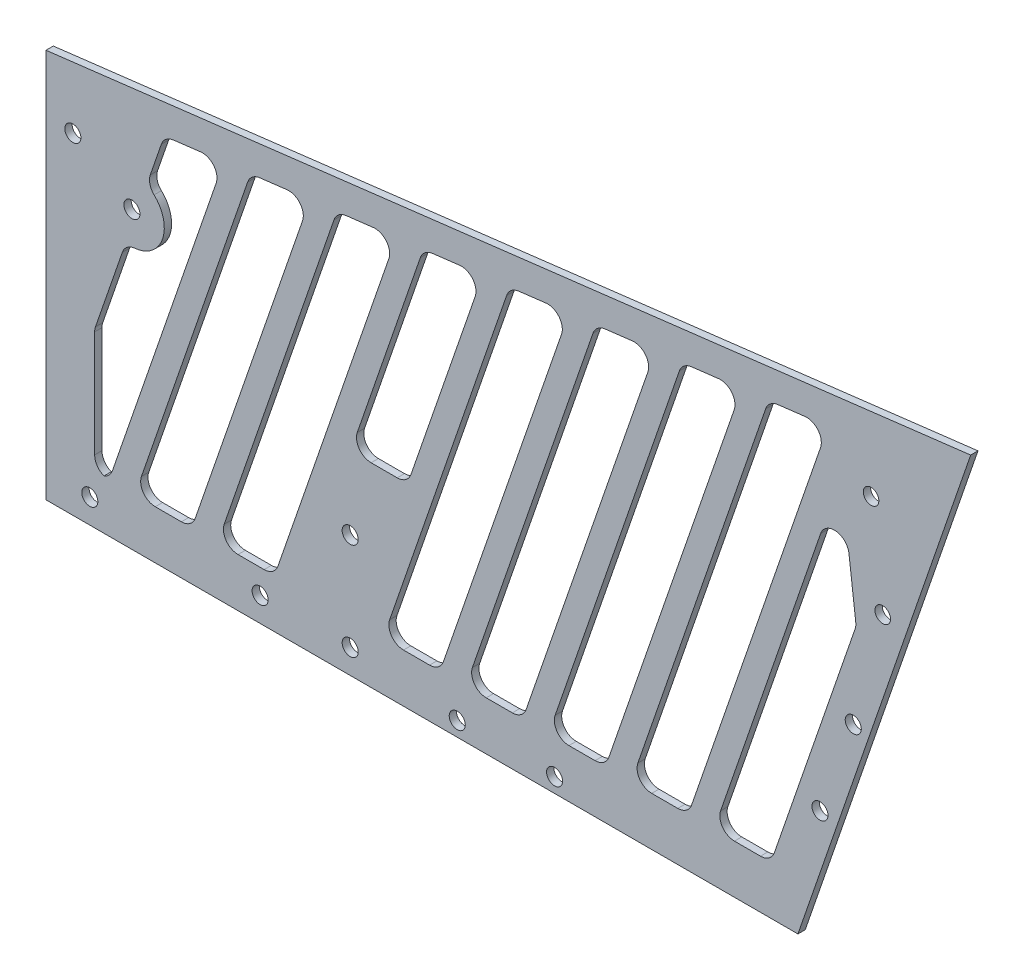
SolidWorks part; units mm, degrees
other "标注1"
sketch "草图8" plane through (190, 0, 1.5) normal (0.4662, -0.1687, 0.8685) x (0.883, 0.0286, -0.4684)
material "自定义塑料"
ref_plane "前视基准面" through (0, 0, 0) normal (0, 0, 1) x (1, 0, 0)
ref_plane "上视基准面" through (0, 0, 0) normal (0, 1, 0) x (1, 0, 0)
ref_plane "右视基准面" through (0, 0, 0) normal (1, 0, 0) x (0, 0, -1)
sketch "草图1" plane through (0, 0, 0) normal (0, 0, 1) x (1, 0, 0)
  line L0 (44, 5) -> (9, 5) construction
  line L1 (0, 0) -> (49, 0)
  line L2 (0, 0) -> (0, 80)
  line L5 (49, 0) -> (154.5, 0)
  line L6 (154.5, 0) -> (190, 102.9694)
  line L7 (0, 80) -> (190, 102.9694)
  circle A0 centre (44, 5) radius 1.65
  circle A1 centre (9, 5) radius 1.65
  circle A2 centre (62.5, 5) radius 1.65
  circle A3 centre (62.5, 25) radius 1.65
  circle A4 centre (84.5, 3) radius 1.65
  circle A5 centre (104.5, 3) radius 1.65
  circle A6 centre (159.0292, 24.1724) radius 1.65
  circle A7 centre (165.8696, 42.9663) radius 1.65
  circle A8 centre (5.5167, 68) radius 1.65
  point P9 (173.819, 56.0356)
  dimension "D3" = 3.3
  dimension "D4" = 190
  dimension "D1" = 49
  dimension "D2" = 80
  dimension "D5" = 5
  dimension "D6" = 35
  dimension "D7" = 105.5
extrude "凸台-拉伸1" add sketch "草图1" along normal blind 1.5
sketch "草图2" plane through (0, 0, 0) normal (0, 0, -1) x (-1, 0, 0)
  circle A0 centre (-17.6548, 60.5226) radius 1.65
  dimension "D1" = 3.3
  dimension "D2" = 60.5226
  dimension "D3" = 17.6548
extrude "切除-拉伸1" cut sketch "草图2" against normal through all
sketch "草图5" plane through (0, 0, 1.5) normal (0, 0, 1) x (1, 0, 0)
  line L0 (0, 80) -> (0, 0) construction
  line L1 (0, 0) -> (154.5, 0) construction
  circle A0 centre (169.5262, 85.385) radius 1.6
  circle A1 centre (171.9266, 65.5296) radius 1.6
  dimension "D1" = 3.2
  dimension "D2" = 169.5262
  dimension "D3" = 171.9266
  dimension "D4" = 65.5296
  dimension "D5" = 85.385
extrude "切除-拉伸3" cut sketch "草图5" against normal through all
sketch "草图6" plane through (0, 0, 0) normal (0, 0, -1) x (-1, 0, 0)
  line L0 (-154.5, 10) -> (0, 10)
  line L1 (-10, 0) -> (-10, 80)
  line L2 (-0.7201, 74.0434) -> (-181.2031, 95.8622)
  line L3 (-181.2031, 95.8622) -> (-148.8277, 1.9556)
  line L4 (0, 0) -> (0, 80)
  line L5 (-154.5, 0) -> (0, 0)
  line L6 (-190, 102.9694) -> (-154.5, 0)
  line L7 (0, 80) -> (-190, 102.9694)
  line L8 (0, 0) -> (0, 80)
  line L9 (-154.5, 0) -> (0, 0)
  line L10 (-190, 102.9694) -> (-154.5, 0)
  line L11 (0, 80) -> (-190, 102.9694)
  line L12 (-162.4894, 93.5999) -> (-167.1453, 55.0868)
  line L13 (-164.2031, 95.8622) -> (-131.8277, 1.9556)
  line L14 (-147.2031, 95.8622) -> (-114.8277, 1.9556)
  line L15 (-130.2031, 95.8622) -> (-97.8277, 1.9556)
  line L16 (-113.2031, 95.8622) -> (-80.8277, 1.9556)
  line L17 (-96.2031, 95.8622) -> (-63.8277, 1.9556)
  line L18 (-79.2031, 95.8622) -> (-46.8277, 1.9556)
  line L19 (-62.2031, 95.8622) -> (-29.8277, 1.9556)
  line L20 (-45.2031, 95.8622) -> (-12.8277, 1.9556)
  line L21 (-28.2031, 95.8622) -> (4.1723, 1.9556)
  line L22 (-166.5666, 95.0474) -> (-134.1912, 1.1408)
  line L23 (-149.5666, 95.0474) -> (-117.1912, 1.1408)
  line L24 (-132.5666, 95.0474) -> (-100.1912, 1.1408)
  line L25 (-115.5666, 95.0474) -> (-83.1912, 1.1408)
  line L26 (-98.5666, 95.0474) -> (-66.1912, 1.1408)
  line L27 (-81.5666, 95.0474) -> (-49.1912, 1.1408)
  line L28 (-64.5666, 95.0474) -> (-32.1912, 1.1408)
  line L29 (-47.5666, 95.0474) -> (-15.1912, 1.1408)
  line L30 (-30.5666, 95.0474) -> (1.8088, 1.1408)
  line L31 (-161.8397, 96.6771) -> (-129.4642, 2.7705)
  line L32 (-144.8397, 96.6771) -> (-112.4642, 2.7705)
  line L33 (-127.8397, 96.6771) -> (-95.4642, 2.7705)
  line L34 (-110.8397, 96.6771) -> (-78.4642, 2.7705)
  line L35 (-93.8397, 96.6771) -> (-61.4642, 2.7705)
  line L36 (-76.8397, 96.6771) -> (-44.4642, 2.7705)
  line L37 (-59.8397, 96.6771) -> (-27.4642, 2.7705)
  line L38 (-42.8397, 96.6771) -> (-10.4642, 2.7705)
  line L39 (-25.8397, 96.6771) -> (6.5358, 2.7705)
  line L40 (-178.8397, 96.6771) -> (-146.4642, 2.7705)
  circle A0 centre (-169.5262, 85.385) radius 1.6 construction
  circle A1 centre (-171.9266, 65.5296) radius 1.6 construction
  circle A2 centre (-165.8696, 42.9663) radius 1.5 construction
  circle A3 centre (-159.0292, 24.1724) radius 1.5 construction
  circle A4 centre (-104.5, 3) radius 1.65 construction
  circle A5 centre (-84.5, 3) radius 1.65 construction
  circle A6 centre (-62.5, 5) radius 1.65 construction
  circle A7 centre (-44, 5) radius 1.65 construction
  circle A8 centre (-62.5, 25) radius 1.65 construction
  circle A9 centre (-9, 5) radius 1.65 construction
  circle A10 centre (-17.6548, 60.5226) radius 1.65 construction
  circle A11 centre (-5.5167, 68) radius 1.65 construction
  circle A12 centre (-169.5262, 85.385) radius 1.6
  circle A13 centre (-171.9266, 65.5296) radius 1.6
  circle A14 centre (-165.8696, 42.9663) radius 1.5
  circle A15 centre (-159.0292, 24.1724) radius 1.5
  circle A16 centre (-104.5, 3) radius 1.65
  circle A17 centre (-84.5, 3) radius 1.65
  circle A18 centre (-62.5, 5) radius 1.65
  circle A19 centre (-44, 5) radius 1.65
  circle A20 centre (-62.5, 25) radius 1.65
  circle A21 centre (-9, 5) radius 1.65
  circle A22 centre (-17.6548, 60.5226) radius 1.65
  circle A23 centre (-5.5167, 68) radius 1.65
  circle A24 centre (-17.6548, 60.5226) radius 6.65
  circle A25 centre (-62.5, 25) radius 6.65
  dimension "D5" = 6
  dimension "D1" = 0
  dimension "D2" = 10
  dimension "D3" = 10
  dimension "D4" = 6
  dimension "D7" = 2.5
  dimension "D8" = 2.5
  dimension "D9" = 5
  dimension "D10" = 2.5
  dimension "D6" = 10
extrude "切除-拉伸4" cut sketch "草图6" against normal blind 10 contours A24 L30 L2 L38 L0 L1 | L2 L37 L0 L29 | L2 L36 L0 L28 | A25 L27 L2 L35 | L2 L34 L0 L26 | L2 L33 L0 L25 | L2 L32 L0 L24 | L2 L31 L0 L23 | L22 L12 L3 L0 region at (153.7758, 42.0864, 0) region at (140.3654, 51.3238, 0) region at (122.9962, 50.2516, 0) region at (105.627, 49.1793, 0) region at (88.2579, 48.1071, 0) region at (74.454, 57.0811, 0) region at (20.6801, 46.912, 0) region at (53.5197, 45.9626, 0) region at (36.1506, 44.8904, 0)
fillet "圆角3" radius 3 37 edges at (89.747, 84.806, 0.75) (77.5264, 83.3286, 0.75) (69.2455, 10, 0.75) (80.9567, 10, 0.75) (107.4863, 86.9505, 0.75) (95.2658, 85.4731, 0.75) (18.2455, 10, 0.75) (29.9567, 10, 0.75) (54.2682, 80.5169, 0.75) (42.0477, 79.0395, 0.75) (35.2455, 10, 0.75) (46.9567, 10, 0.75) (72.0076, 82.6614, 0.75) (59.7871, 81.1841, 0.75) (120.2455, 10, 0.75) (131.9567, 10, 0.75) (160.7044, 93.3841, 0.75) (148.4839, 91.9067, 0.75) (16.4115, 53.9898, 0.75) (10, 35.3929, 0.75) (10, 10, 0.75) (12.9567, 10, 0.75) (36.5289, 78.3723, 0.75) (24.3084, 76.895, 0.75) (20.7016, 66.4335, 0.75) (103.2455, 10, 0.75) (114.9567, 10, 0.75) (142.965, 91.2396, 0.75) (130.7445, 89.7622, 0.75) (86.2455, 10, 0.75) (97.9567, 10, 0.75) (125.2257, 89.095, 0.75) (113.0051, 87.6177, 0.75) (163.4184, 85.9157, 0.75) (137.2455, 10, 0.75) (166.4588, 60.7657, 0.75) (148.9567, 10, 0.75)
fillet "圆角4" radius 5 1 edges at (69.1497, 25.0627, 0.75)
sketch "草图7" plane through (0, 0, 1.5) normal (0, 0, 1) x (1, 0, 0)
  line L1 (76.1407, 40) -> (59.1407, 40)
  line L2 (76.1407, 40) -> (76.1407, 30)
  line L3 (76.1407, 30) -> (59.1407, 30)
  line L4 (59.1407, 40) -> (59.1407, 30)
  line L6 (0, 0) -> (154.5, 0) construction
  line L7 (94.6538, 83.698) -> (70.6169, 13.9778) construction
  dimension "D1" = 40
  dimension "D2" = 17
  dimension "D3" = 10
extrude "凸台-拉伸2" add sketch "草图7" against normal up to surface (1.5 mm away) up to face at (88.1355, 48.0309, 0)
fillet "圆角5" radius 3 2 edges at (74.2996, 40, 0.75) (62.5884, 40, 0.75)
